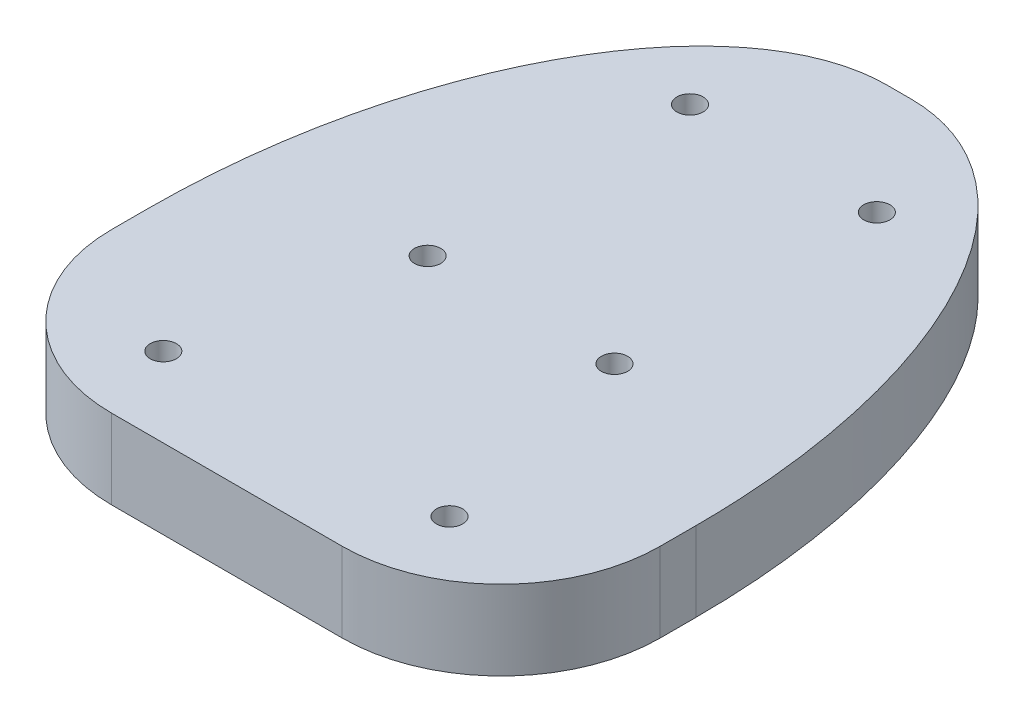
SolidWorks part; units mm, degrees
ref_plane "Front Plane" through (0, 0, 0) normal (0, 0, 1) x (1, 0, 0)
ref_plane "Top Plane" through (0, 0, 0) normal (0, 1, 0) x (1, 0, 0)
ref_plane "Right Plane" through (0, 0, 0) normal (1, 0, 0) x (0, 0, -1)
sketch "Sketch1" plane through (0, 0, 0) normal (0, 1, 0) x (1, 0, 0)
  line L1 (-50, -50) -> (50, -50)
  line L2 (-50, -50) -> (-50, 50)
  line L3 (-50, 50) -> (50, 50)
  line L4 (50, -50) -> (50, 50)
  line L5 (-50, -50) -> (50, 50) construction
  line L6 (-50, 50) -> (50, -50) construction
  point P0 (0, 0)
  dimension "D1" = 100
extrude "Boss-Extrude1" add sketch "Sketch1" along normal blind 10
sketch "Sketch2" plane through (0, 0, 0) normal (0, -1, 0) x (1, 0, 0)
  circle A0 centre (-26.5, 28.5) radius 4.005
  circle A1 centre (26.5, 28.5) radius 4.005
  circle A2 centre (0, -26.5) radius 4.005
  dimension "D1" = 8.01
extrude "Cut-Extrude1" cut sketch "Sketch2" against normal offset from surface (7 mm away) 3 up to face at (0, 10, 0)
sketch "Sketch3" plane through (0, 10, 0) normal (0, 1, 0) x (1, 0, 0)
  circle A0 centre (-11.75, 20) radius 1.65
  circle A1 centre (11.75, 20) radius 1.65
  circle A2 centre (11.75, -13) radius 1.65
  circle A3 centre (18, -40) radius 1.65
  circle A4 centre (-18, -40) radius 1.65
  circle A5 centre (-11.75, -13) radius 1.65
  dimension "D1" = 3.3
extrude "Cut-Extrude2" cut sketch "Sketch3" against normal through all
sketch "Sketch4" plane through (0, 10, 0) normal (0, 1, 0) x (1, 0, 0)
  line L0 (-34.5, -50) -> (-34.5, 34.5)
  line L1 (-50, -50) -> (50, -50) construction
  line L3 (34.5, -50) -> (34.5, 34.5)
  line L4 (34.5, 34.5) -> (-34.5, 34.5)
  line L7 (-34.5, -50) -> (34.5, -50)
  circle A0 centre (-26.5, -28.5) radius 4 construction
  circle A1 centre (26.5, -28.5) radius 4 construction
  circle A2 centre (0, 26.5) radius 4 construction
  dimension "D1" = 8
  dimension "D2" = 8
  dimension "D3" = 8
extrude "Cut-Extrude3" cut sketch "Sketch4" against normal through all flip side to cut
fillet "Fillet1" radius 20 2 edges at (34.5, 5, 50) (-34.5, 5, 50)
fillet "Fillet2" radius 60 2 edges at (34.5, 5, -34.5) (-34.5, 5, -34.5) second distance 33 first distance on face at (34.5, 5, -2.25) first distance on face at (-34.5, 5, -2.25)
